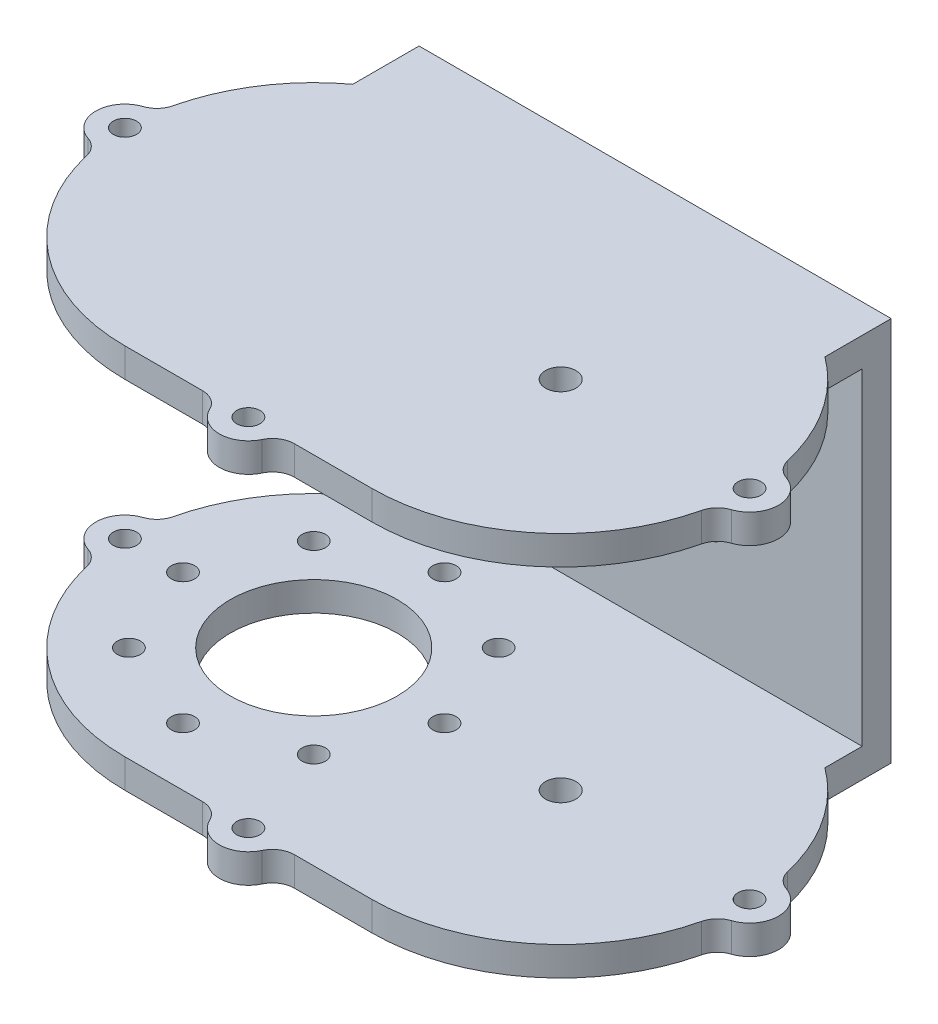
SolidWorks part; units mm, degrees
ref_plane "前视基准面" through (0, 0, 0) normal (0, 0, 1) x (1, 0, 0)
ref_plane "上视基准面" through (0, 0, 0) normal (0, 1, 0) x (1, 0, 0)
ref_plane "右视基准面" through (0, 0, 0) normal (1, 0, 0) x (0, 0, -1)
sketch "草图1" plane through (0, 0, 0) normal (0, 0, 1) x (1, 0, 0)
  line L1 (-32.5, -26.5) -> (32.5, -26.5)
  line L2 (-32.5, -26.5) -> (-32.5, 26.5)
  line L3 (-32.5, 26.5) -> (32.5, 26.5)
  line L4 (32.5, -26.5) -> (32.5, 26.5)
  line L5 (0, 26.5) -> (0, -26.5) construction
  line L6 (-32.5, 0) -> (32.5, 0) construction
  circle A0 centre (0, 0) radius 13.5 construction
  circle A1 centre (0, 13.5) radius 1.6
  circle A3 centre (11.6913, 6.75) radius 1.6
  circle A4 centre (11.6913, -6.75) radius 1.6
  circle A5 centre (0, -13.5) radius 1.6
  circle A6 centre (-11.6913, -6.75) radius 1.6
  circle A7 centre (-11.6913, 6.75) radius 1.6
  point P18 (0, 0)
  dimension "D1" = 3.2
  dimension "D2" = 27
  dimension "D4" = 53
  dimension "D5" = 65
  dimension "D3" = 6
extrude "凸台-拉伸1" add sketch "草图1" along normal blind 4
sketch "草图3" plane through (0, 0, 4) normal (0, 0, 1) x (1, 0, 0)
  line L1 (28.5, 22.5) -> (-28.5, 22.5)
  line L3 (-28.5, -22.5) -> (28.5, -22.5)
  line L4 (32.5, -26.5) -> (32.5, 26.5)
  line L5 (32.5, 26.5) -> (-32.5, 26.5)
  line L6 (-32.5, 26.5) -> (-32.5, -26.5)
  line L7 (-32.5, -26.5) -> (32.5, -26.5)
  line L8 (32.5, -26.5) -> (32.5, -22.5)
  line L9 (32.5, 26.5) -> (-32.5, 26.5)
  line L10 (-32.5, 26.5) -> (-32.5, 22.5)
  line L11 (-32.5, -26.5) -> (32.5, -26.5)
  line L12 (-28.5, 22.5) -> (-32.5, 22.5)
  line L13 (28.5, 22.5) -> (32.5, 22.5)
  line L14 (28.5, -22.5) -> (32.5, -22.5)
  line L15 (-28.5, -22.5) -> (-32.5, -22.5)
  line L16 (32.5, 22.5) -> (32.5, 26.5)
  line L17 (-28.5, 22.5) -> (-28.5, -22.5) construction
  line L18 (28.5, -22.5) -> (28.5, 22.5) construction
  line L19 (32.5, -26.5) -> (32.5, 26.5) construction
  line L20 (-32.5, -22.5) -> (-32.5, -26.5)
  line L21 (-32.5, 26.5) -> (-32.5, -26.5) construction
  dimension "D1" = 0
  dimension "D2" = 4
extrude "凸台-拉伸2" add sketch "草图3" along normal blind 60
sketch "草图5" plane through (0, -26.5, 0) normal (0, -1, 0) x (1, 0, 0)
  line L0 (0, 0) -> (0, 64) construction
  line L1 (-32.5, 64) -> (32.5, 64) construction
  circle A0 centre (-17, 30) radius 18 construction
  circle A1 centre (-17, 48) radius 1.6
  circle A2 centre (-17, 30) radius 11.5
  circle A3 centre (-4.2721, 42.7279) radius 1.6
  circle A4 centre (1, 30) radius 1.6
  circle A5 centre (-4.2721, 17.2721) radius 1.6
  circle A6 centre (-17, 12) radius 1.6
  circle A7 centre (-29.7279, 17.2721) radius 1.6
  circle A8 centre (-35, 30) radius 1.6
  circle A9 centre (-29.7279, 42.7279) radius 1.6
  point P22 (-17, 30)
  dimension "D1" = 3.2
  dimension "D2" = 36
  dimension "D3" = 23
  dimension "D5" = 34
  dimension "D6" = 34
  dimension "D4" = 8
extrude "切除-拉伸1" cut sketch "草图5" against normal up to surface (4 mm away) up to face at (0, -22.5, 34)
sketch "草图6" plane through (0, -26.5, 0) normal (0, -1, 0) x (1, 0, 0)
  line L0 (-32.5, 64) -> (-32.5, 0) construction
  line L2 (-17, 56) -> (17, 56)
  line L3 (0, 0) -> (0, 56) construction
  line L9 (-32.5, 0) -> (32.5, 0)
  line L10 (32.5, 0) -> (32.5, 64)
  line L11 (32.5, 64) -> (-32.5, 64)
  line L12 (-32.5, 64) -> (-32.5, 0)
  line L13 (-32.5, 0) -> (32.5, 0)
  line L14 (32.5, 0) -> (32.5, 64)
  line L15 (32.5, 64) -> (-32.5, 64)
  line L16 (-32.5, 64) -> (-32.5, 0)
  arc A0 (-32.5, 9.1254) -> (-17, 56) centre (-17, 30) cw
  circle A1 centre (-17, 30) radius 11.5 construction
  arc A2 (32.5, 9.1254) -> (17, 56) centre (17, 30) ccw
  circle A3 centre (-35, 30) radius 1.6
  line M12 (-32.5, 64) -> (-32.5, 0)
  line M14 (32.5, 0) -> (32.5, 64)
  line M15 (32.5, 64) -> (-32.5, 64)
  dimension "D3" = 3.2
  dimension "D1" = 26
  dimension "D4" = 18
  dimension "D2" = 0
extrude "切除-拉伸2" cut sketch "草图6" against normal blind 69 contours A2 A0 L2 M14 M15 M12 region at (0, -26.5, 59.5109)
extrude "凸台-拉伸3" add sketch "草图6<3>" against normal up to surface (4 mm away) contours A0 L16 | L14 A2 region at (-36.8304, -26.5, 30) region at (36.7824, -26.5, 30) up to face at (-2.6721, -22.5, 17.2721)
sketch "草图6<3>" plane through (0, -26.5, 0) normal (0, -1, 0) x (1, 0, 0) same geometry as "草图6"
extrude "凸台-拉伸4" add sketch "草图6<4>" against normal up to surface (53 mm away) from surface contours A0 L16 | L14 A2 | A3 region at (-36.8304, -26.5, 30) region at (36.7824, -26.5, 30) region at (-35, -26.5, 30) up to face at (0, 26.5, 36.0409) starting at face at (0, 22.5, 37.3742)
sketch "草图6<4>" plane through (0, -26.5, 0) normal (0, -1, 0) x (1, 0, 0) same geometry as "草图6"
sketch "草图7" plane through (0, 26.5, 0) normal (0, 1, 0) x (1, 0, 0)
  circle A0 centre (17, -30) radius 2.1
  arc A1 (17, -56) -> (32.5, -9.1254) centre (17, -30) ccw construction
  dimension "D1" = 4.2
extrude "切除-拉伸3" cut sketch "草图7" against normal blind 100
sketch "草图8" plane through (0, -26.5, 0) normal (0, -1, 0) x (1, 0, 0)
  line L0 (-17, 56) -> (17, 56) construction
  line L1 (-4, 56) -> (-1.6, 56)
  line L2 (1.6, 56) -> (4, 56)
  line L3 (0, 56) -> (0, 0) construction
  arc A0 (-4, 56) -> (4, 56) centre (0, 56) cw
  circle A1 centre (0, 56) radius 1.6
  arc A2 (42.6923, 33.9881) -> (42.6923, 26.0119) centre (43, 30) cw
  arc A3 (32.5, 9.1254) -> (17, 56) centre (17, 30) ccw construction
  circle A4 centre (43, 30) radius 1.6
  arc A5 (42.6923, 26.0119) -> (42.9508, 28.4008) centre (17, 30) ccw
  arc A6 (42.9508, 31.5992) -> (42.6923, 33.9881) centre (17, 30) ccw
  arc A7 (-42.9508, 31.5992) -> (-42.6923, 33.9881) centre (-17, 30) cw
  arc A8 (-42.6923, 26.0119) -> (-42.9508, 28.4008) centre (-17, 30) cw
  circle A9 centre (-43, 30) radius 1.6
  arc A10 (-42.6923, 33.9881) -> (-42.6923, 26.0119) centre (-43, 30) ccw
  point P10 (17, 30)
  arc M13 (32.5, 9.1254) -> (17, 56) centre (17, 30) ccw
  line M14 (17, 56) -> (-17, 56)
  arc M15 (-17, 56) -> (-32.5, 9.1254) centre (-17, 30) ccw
  dimension "D1" = 3.2
  dimension "D2" = 4
  dimension "D3" = 3.2
  dimension "D4" = 4
extrude "凸台-拉伸6" add sketch "草图8" against normal up to surface (4 mm away) contours A1 A0 M14 | A10 A9 M15 | A4 A2 M13 region at (0, -26.5, 57.8917) region at (44.8218, -26.5, 30) region at (-44.8218, -26.5, 30) up to face at (19.1, -22.5, 30)
extrude "凸台-拉伸7" add sketch "草图8<4>" against normal up to surface (53 mm away) from surface contours A1 A0 M14 | A4 A2 M13 | A10 A9 M15 region at (0, -26.5, 57.8917) region at (44.8218, -26.5, 30) region at (-44.8218, -26.5, 30) up to face at (17, 26.5, 32.1) starting at face at (14.9, 22.5, 30)
sketch "草图8<4>" plane through (0, -26.5, 0) normal (0, -1, 0) x (1, 0, 0) same geometry as "草图8"
extrude "切除-拉伸4" cut sketch "草图8<5>" against normal blind 70 contours L3 A1 M14 | L3 A1 M14 | A4 M13 | A9 M15 region at (-0.6791, -26.5, 55.3209) region at (0.6791, -26.5, 55.3209) region at (-42.3121, -26.5, 30) region at (42.3121, -26.5, 30)
sketch "草图8<5>" plane through (0, -26.5, 0) normal (0, -1, 0) x (1, 0, 0) same geometry as "草图8"
fillet "圆角1" radius 3 12 edges at (-42.6923, 24.5, 26.0119) (-42.6923, 24.5, 33.9881) (-4, 24.5, 56) (4, 24.5, 56) (42.6923, 24.5, 26.0119) (42.6923, 24.5, 33.9881) (42.6923, -24.5, 33.9881) (42.6923, -24.5, 26.0119) (-42.6923, -24.5, 26.0119) (-42.6923, -24.5, 33.9881) (-4, -24.5, 56) (4, -24.5, 56)
